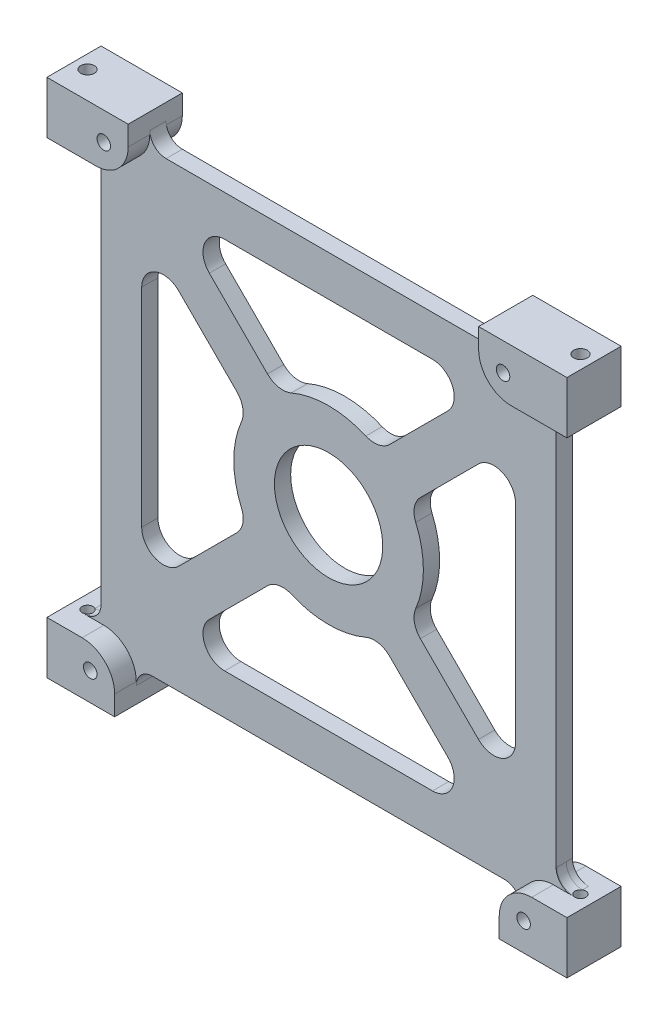
SolidWorks part; units mm, degrees
material "7075-T6 (SN)"
ref_plane "Front Plane" through (0, 0, 0) normal (0, 0, 1) x (1, 0, 0)
ref_plane "Top Plane" through (0, 0, 0) normal (0, 1, 0) x (1, 0, 0)
ref_plane "Right Plane" through (0, 0, 0) normal (1, 0, 0) x (0, 0, -1)
sketch "Sketch1" plane through (0, 0, 0) normal (0, 0, 1) x (1, 0, 0)
  line L0 (-38, 42) -> (-38, 38)
  line L1 (48, -48) -> (-48, -48)
  line L2 (48, -48) -> (48, 48)
  line L3 (48, 48) -> (-48, 48)
  line L4 (-48, -48) -> (-48, 48)
  line L5 (48, -48) -> (-48, 48) construction
  line L6 (48, 48) -> (-48, -48) construction
  line L7 (42, -42) -> (-42, -42)
  line L8 (42, -42) -> (42, 42)
  line L9 (42, 42) -> (-42, 42)
  line L10 (-42, -42) -> (-42, 42)
  line L11 (42, -42) -> (-42, 42) construction
  line L12 (42, 42) -> (-42, -42) construction
  line L13 (-38, 38) -> (-42, 38)
  line L14 (42, 38) -> (38, 38)
  line L15 (38, 38) -> (38, 42)
  line L16 (38, -42) -> (38, -38)
  line L17 (38, -38) -> (42, -38)
  line L18 (-42, -38) -> (-38, -38)
  line L19 (-38, -38) -> (-38, -42)
  point P0 (0, 0)
  point P6 (0, 0)
  point P26 (0, 0)
  dimension "D1" = 96
  dimension "D2" = 96
  dimension "D3" = 6
  dimension "D4" = 84
  dimension "D5" = 10
  dimension "D6" = 4
extrude "Boss-Extrude1" add sketch "Sketch1" along normal blind 10 contours L4 L1 L2 L3 L7 L10 L9 L8 region at (0, -46.6424, 0)
sketch "Sketch4" plane through (0, 0, 10) normal (0, 0, 1) x (1, 0, 0)
  line L0 (36.2, 42.85) -> (-37.5, 42.85) construction
  line L1 (40, -42.85) -> (-40, -42.85) construction
  line L2 (-40, -42.85) -> (-40, 42.85) construction
  line L3 (-40, 42.85) -> (-37.5, 42.85) construction
  line L4 (40, -42.85) -> (40, 42.85) construction
  line L5 (40, 42.85) -> (36.2, 42.85) construction
  line L6 (-40, 42.85) -> (40, -42.85) construction
  point P4 (0, 0)
  dimension "D1" = 73.7
  dimension "D2" = 2.5
  dimension "D3" = 85.7
  dimension "D4" = 3.8
sketch_block_instance "Block1-1"
sketch_block "Block2"
sketch "Sketch5" plane through (0, 0, 10) normal (0, 0, 1) x (1, 0, 0)
  line L0 (40.7, 38.35) -> (42, 38.35)
  line L1 (-42, 47.35) -> (-33, 47.35)
  line L2 (-42, 47.35) -> (-42, 38.35)
  line L3 (-42, 38.35) -> (-33, 38.35)
  line L4 (-33, 47.35) -> (-33, 38.35)
  line L5 (-42, 47.35) -> (-33, 38.35) construction
  line L6 (-42, 38.35) -> (-33, 47.35) construction
  line L7 (-35.5, -47.35) -> (-44.5, -47.35)
  line L8 (-35.5, -47.35) -> (-35.5, -38.35)
  line L9 (-35.5, -38.35) -> (-44.5, -38.35)
  line L10 (-44.5, -47.35) -> (-44.5, -38.35)
  line L11 (-35.5, -47.35) -> (-44.5, -38.35) construction
  line L12 (-35.5, -38.35) -> (-44.5, -47.35) construction
  line L13 (44.5, -47.35) -> (35.5, -47.35)
  line L14 (44.5, -47.35) -> (44.5, -38.35)
  line L15 (44.5, -38.35) -> (35.5, -38.35)
  line L16 (35.5, -47.35) -> (35.5, -38.35)
  line L17 (44.5, -47.35) -> (35.5, -38.35) construction
  line L18 (44.5, -38.35) -> (35.5, -47.35) construction
  line L19 (40.7, 38.35) -> (31.7, 38.35)
  line L20 (40.7, 38.35) -> (40.7, 47.35)
  line L21 (40.7, 47.35) -> (31.7, 47.35)
  line L22 (31.7, 38.35) -> (31.7, 47.35)
  line L23 (40.7, 38.35) -> (31.7, 47.35) construction
  line L24 (40.7, 47.35) -> (31.7, 38.35) construction
  line L25 (42, -42) -> (42, 42) construction
  line L26 (42, 38.35) -> (42, 42)
  line L27 (42, 42) -> (40.7, 42)
  line L28 (42, 42) -> (-42, 42) construction
  point P0 (-37.5, 42.85)
  point P1 (36.2, 42.85)
  point P3 (40, -42.85)
  point P5 (-40, -42.85)
  point P7 (-37.5, 42.85)
  point P13 (-40, -42.85)
  point P18 (40, -42.85)
  point P23 (36.2, 42.85)
  line M13 (42, -42) -> (-42, -42)
  line M14 (-42, -42) -> (-42, 42)
  line M15 (-42, 42) -> (42, 42)
  line M16 (42, 42) -> (42, -42)
  dimension "D1" = 9
  dimension "D2" = 9
  dimension "D3" = 9
  dimension "D4" = 9
  dimension "D5" = 9
  dimension "D6" = 9
  dimension "D7" = 9
  dimension "D8" = 9
extrude "Boss-Extrude2" add sketch "Sketch5" against normal up to surface (10 mm away) contours L22 L19 L20 M15 | L20 L0 M16 M15 | L4 L3 M15 M14 | L8 L9 M14 M13 | L16 L15 M13 M16 region at (41.35, 40.175, 10) region at (36.2, 40.175, 10) region at (38.75, -40.175, 10) region at (-37.5, 40.175, 10) region at (-38.75, -40.175, 10) up to face at (0, 0, 0)
fillet "Fillet1" radius 3 8 edges at (-42, 38.35, 5) (-33, 42, 5) (31.7, 42, 5) (42, 38.35, 5) (35.5, -42, 5) (42, -38.35, 5) (-35.5, -42, 5) (-42, -38.35, 5)
hole_wizard "M3 Tapped Hole1" positions "3DSketch1" profile "Sketch6" tap size "M3" standard "ISO" end condition through all
sketch3d "3DSketch1"
  point P0 (-37.5, 42.85, 10)
  point P3 (36.2, 42.85, 10)
  point P6 (-40, -42.85, 10)
  point P9 (40, -42.85, 10)
  point P12 (0, 0, 0)
  point P13 (0, 0, 0)
cosmetic thread "Hole Thread1" parameters "D2"=3
cosmetic thread "Hole Thread2" parameters "D2"=3
cosmetic thread "Hole Thread3" parameters "D2"=3
cosmetic thread "Hole Thread4" parameters "D2"=3
sketch "Sketch6" plane through (-37.5, 42.85, 10) normal (1, 0, 0) x (0, -1, 0)
  line L0 (0, 0) -> (0, 10)
  line L1 (0, 10) -> (1.25, 10)
  line L2 (1.25, 10) -> (1.25, 0)
  line L5 (1.25, 0) -> (0, 0)
  line L11 (0, -6.35) -> (0, 107.95) construction
  dimension "Thru Tap Drill Dia." = 2.5
  dimension "Thru Tap Drill Depth" = 10
ref_plane "Plane1" through (0, 0, 5) normal (0, 0, -1) x (-1, 0, 0)
sketch "Sketch7" plane through (48, 0, 0) normal (1, 0, 0) x (0, 0, -1)
  line L0 (-5, -48) -> (-5, -32) construction
  line L1 (-10, -48) -> (0, -48) construction
  line L2 (-5, 48) -> (-5, 32) construction
  line L3 (-10, 48) -> (0, 48) construction
  dimension "D1" = 16
  dimension "D2" = 16
ref_plane "Plane2" through (0, 0, 0) normal (0.7071, 0.7071, 0) x (0.7071, -0.7071, 0)
ref_plane "Plane3" through (0, 0, 0) normal (0.7071, -0.7071, 0) x (0, 0, -1)
ref_axis "Axis1" through (0, 0, -0.5) along (0, 0, 1)
sketch "Sketch9" plane through (0, 0, 10) normal (0, 0, 1) x (1, 0, 0)
  line L0 (39, 38.35) -> (43, 38.35)
  line L1 (46, 35.35) -> (46, -35.35)
  line L2 (43, -38.35) -> (39, -38.35)
  line L3 (48, -48) -> (48, 48) construction
  line L24 (39, 38.35) -> (31.7, 38.35)
  line L25 (42, -35.35) -> (42, 35.35)
  line L26 (35.5, -38.35) -> (39, -38.35)
  line L27 (35.5, -42) -> (35.5, -38.35)
  line L28 (-32.5, -45) -> (32.5, -45)
  line L29 (-35.5, -38.35) -> (-35.5, -42)
  line L30 (-42, -38.35) -> (-35.5, -38.35)
  line L31 (-45, 35.35) -> (-45, -35.35)
  line L32 (-33, 38.35) -> (-42, 38.35)
  line L33 (-33, 42) -> (-33, 38.35)
  line L34 (28.7, 45) -> (-30, 45)
  line L35 (31.7, 38.35) -> (31.7, 42)
  line L36 (39, 38.35) -> (31.7, 38.35)
  line L37 (42, -35.35) -> (42, 35.35)
  line L38 (35.5, -38.35) -> (39, -38.35)
  line L39 (35.5, -42) -> (35.5, -38.35)
  line L40 (-32.5, -45) -> (32.5, -45)
  line L41 (-35.5, -38.35) -> (-35.5, -42)
  line L42 (-42, -38.35) -> (-35.5, -38.35)
  line L43 (-45, 35.35) -> (-45, -35.35)
  line L44 (-33, 38.35) -> (-42, 38.35)
  line L45 (-33, 42) -> (-33, 38.35)
  line L46 (28.7, 45) -> (-30, 45)
  line L47 (31.7, 38.35) -> (31.7, 42)
  arc A0 (46, -35.35) -> (43, -38.35) centre (43, -35.35) cw
  arc A1 (43, 38.35) -> (46, 35.35) centre (43, 35.35) cw
  circle A13 centre (40, -42.85) radius 1.7
  circle A14 centre (40, -42.85) radius 1.7
  circle A15 centre (-40, -42.85) radius 1.7
  circle A16 centre (-40, -42.85) radius 1.7
  circle A17 centre (36.2, 42.85) radius 1.7
  circle A18 centre (36.2, 42.85) radius 1.7
  circle A19 centre (-37.5, 42.85) radius 1.7
  circle A20 centre (-37.5, 42.85) radius 1.7
  arc A28 (42, 35.35) -> (39, 38.35) centre (39, 35.35) ccw
  arc A29 (42, 35.35) -> (39, 38.35) centre (39, 35.35) ccw
  arc A30 (32.5, -45) -> (35.5, -42) centre (32.5, -42) ccw
  arc A31 (-35.5, -42) -> (-32.5, -45) centre (-32.5, -42) ccw
  arc A32 (-45, -35.35) -> (-42, -38.35) centre (-42, -35.35) ccw
  arc A33 (-42, 38.35) -> (-45, 35.35) centre (-42, 35.35) ccw
  arc A34 (-30, 45) -> (-33, 42) centre (-30, 42) ccw
  arc A35 (31.7, 42) -> (28.7, 45) centre (28.7, 42) ccw
  arc A36 (39, -38.35) -> (42, -35.35) centre (39, -35.35) ccw
  arc A37 (39, -38.35) -> (42, -35.35) centre (39, -35.35) ccw
  arc A38 (32.5, -45) -> (35.5, -42) centre (32.5, -42) ccw
  arc A39 (-35.5, -42) -> (-32.5, -45) centre (-32.5, -42) ccw
  arc A40 (-45, -35.35) -> (-42, -38.35) centre (-42, -35.35) ccw
  arc A41 (-42, 38.35) -> (-45, 35.35) centre (-42, 35.35) ccw
  arc A42 (-30, 45) -> (-33, 42) centre (-30, 42) ccw
  arc A43 (31.7, 42) -> (28.7, 45) centre (28.7, 42) ccw
  dimension "D7" = 3
  dimension "D6" = 2
  dimension "D1" = 0
  dimension "D2" = 0
  dimension "D3" = 0
  dimension "D4" = 0
  dimension "D5" = 0
extrude "Cut-Extrude1" cut sketch "Sketch9" against normal blind 2.5 contours A1 L0 L2 A0 L1 | L47 A43 L46 A42 L45 | L44 A41 L43 A40 L42 | L41 A39 L40 A38 L39 region at (-1.3591, -0.231, 10) region at (43.9496, 0, 10)
mirror "Mirror1" about plane through (0, 0, 5) normal (0, 0, -1) of "Cut-Extrude1"
sketch "Sketch10" plane through (0, -48, 0) normal (0, -1, 0) x (1, 0, 0)
  line L0 (-48, 5) -> (-45.5, 5) construction
  line L1 (-48, 10) -> (-48, 0) construction
  line L2 (48, 5) -> (45.5, 5) construction
  line L3 (48, 10) -> (48, 0) construction
  dimension "D1" = 2.5
  dimension "D2" = 2.5
hole_wizard "M3 Tapped Hole3" positions "3DSketch3" profile "Sketch11" tap size "M3" standard "ISO"
sketch3d "3DSketch3"
  point P0 (45.5, -48, 5)
  point P3 (-45.5, -48, 5)
sketch "Sketch11" plane through (45.5, -48, 5) normal (1, 0, 0) x (0, 0, -1)
  line L0 (0, 0) -> (0, 10.2511)
  line L1 (0, 10.2511) -> (1.25, 9.5)
  line L2 (1.25, 9.5) -> (1.25, 0)
  line L5 (1.25, 0) -> (0, 0)
  line L10 (0, 10.2511) -> (-1.25, 9.5) construction
  line L11 (0, -6.35) -> (0, 107.95) construction
  dimension "Tap Drill Dia." = 2.5
  dimension "Tap Drill Depth" = 9.5
  dimension "Drill Angle" = 118
cosmetic thread "Hole Thread7" parameters "D1"=8, "D2"=3
cosmetic thread "Hole Thread8" parameters "D1"=8, "D2"=3
mirror "Mirror2" about plane through (0, 0, 0) normal (0, 1, 0) of "M3 Tapped Hole3"
sketch "Sketch12" plane through (48, 0, 0) normal (1, 0, 0) x (0, 0, -1)
  line L0 (-2.8545, 17.3008) -> (-2.8545, 16.9808) construction
  line L1 (-1.8545, 12.4908) -> (-1.8545, 18.0408) construction
  line L2 (-0.6545, 10.1908) -> (1.2455, 10.1908) construction
  line L3 (-0.6545, 20.3408) -> (1.2455, 20.3408) construction
  line L4 (-1.1757, -7.1497) -> (-1.1757, -18.1479) construction
  line L5 (-2.8545, 17.3008) -> (-2.8545, 16.9808)
  line L6 (-1.8545, 12.4908) -> (-1.8545, 18.0408)
  line L7 (-0.6545, 10.1908) -> (1.2455, 10.1908)
  line L8 (-0.6545, 20.3408) -> (1.2455, 20.3408)
  line L9 (-1.1757, -7.1497) -> (-1.1757, -18.1479)
sketch "Sketch13" plane through (0, 0, 10) normal (0, 0, 1) x (1, 0, 0)
  line L0 (-48, -48) -> (-48, 48) construction
  line L1 (-48, 38.35) -> (48, 38.35)
  line L2 (-48, 38.35) -> (-48, -38.35)
  line L3 (-48, -38.35) -> (48, -38.35)
  line L4 (48, 38.35) -> (48, -38.35)
  line L5 (48, -48) -> (48, 48) construction
  line L6 (-42, 38.35) -> (-33, 38.35) construction
  line L7 (-35.5, -38.35) -> (-42, -38.35) construction
  line L8 (48, 48) -> (-48, 48) construction
  line L9 (-33, 38.35) -> (31.7, 38.35)
  line L10 (-33, 38.35) -> (-33, 48)
  line L11 (-33, 48) -> (31.7, 48)
  line L12 (31.7, 38.35) -> (31.7, 48)
  line L13 (31.7, 38.35) -> (31.7, 42) construction
  line L14 (48, -48) -> (-48, -48) construction
  line L15 (-35.5, -38.35) -> (35.5, -38.35)
  line L16 (-35.5, -38.35) -> (-35.5, -48)
  line L17 (-35.5, -48) -> (35.5, -48)
  line L18 (35.5, -38.35) -> (35.5, -48)
  line L19 (35.5, -42) -> (35.5, -38.35) construction
  point P21 (31.7, 40.175)
  arc M13 (28.7, 45) -> (31.7, 42) centre (28.7, 42) cw
  line M14 (31.7, 42) -> (31.7, 38.35)
  line M15 (31.7, 38.35) -> (43, 38.35)
  arc M16 (43, 38.35) -> (46, 35.35) centre (43, 35.35) cw
  line M17 (46, 35.35) -> (46, -35.35)
  arc M18 (46, -35.35) -> (43, -38.35) centre (43, -35.35) cw
  line M19 (43, -38.35) -> (35.5, -38.35)
  line M20 (35.5, -38.35) -> (35.5, -42)
  arc M21 (35.5, -42) -> (32.5, -45) centre (32.5, -42) cw
  line M22 (32.5, -45) -> (-32.5, -45)
  arc M23 (-32.5, -45) -> (-35.5, -42) centre (-32.5, -42) cw
  line M24 (-35.5, -42) -> (-35.5, -38.35)
  line M25 (-35.5, -38.35) -> (-42, -38.35)
  arc M26 (-42, -38.35) -> (-45, -35.35) centre (-42, -35.35) cw
  line M27 (-45, -35.35) -> (-45, 35.35)
  arc M28 (-45, 35.35) -> (-42, 38.35) centre (-42, 35.35) cw
  line M29 (-42, 38.35) -> (-33, 38.35)
  line M30 (-33, 38.35) -> (-33, 42)
  arc M31 (-33, 42) -> (-30, 45) centre (-30, 42) cw
  line M32 (-30, 45) -> (28.7, 45)
  line M37 (-48, 48) -> (-48, -48)
  line M38 (-48, -48) -> (48, -48)
  line M39 (48, -48) -> (48, 48)
  line M40 (48, 48) -> (-48, 48)
extrude "Cut-Extrude3" cut sketch "Sketch13" against normal blind 10 contours L12 L10 M13 M40 M31 M32 | L1 M30 M14 M13 M32 M31 | L3 L1 M37 M26 M27 M28 | L3 L1 M25 M19 M18 M17 M16 M15 M29 M28 M27 M26 | L3 L1 M18 M39 M16 M17 | L18 L16 M21 M22 M23 M38 | L3 M24 M23 M22 M21 M20 region at (-46.4642, 0, 10) region at (0.5, 0, 10) region at (-0.65, 41.6509, 10) region at (-0.65, 46.4577, 10) region at (0, -41.6531, 10) region at (0, -46.4613, 10) region at (46.959, 0, 10)
sketch "Sketch15" plane through (0, 0, 5) normal (0, 0, -1) x (-1, 0, 0)
  line L0 (-34.5, 19.1863) -> (-34.5, -19.1863)
  line L1 (42, 38.35) -> (-42, 38.35)
  line L2 (42, 38.35) -> (42, -38.35)
  line L3 (42, -38.35) -> (-42, -38.35)
  line L4 (-42, 38.35) -> (-42, -38.35)
  line L5 (-48, -38.35) -> (-35.5, -38.35) construction
  line L6 (48, 38.35) -> (48, 48) construction
  line L7 (48, 38.35) -> (33, 38.35) construction
  line L8 (-48, 38.35) -> (-48, 48) construction
  line L9 (33, 48) -> (33, 38.35) construction
  line L10 (33, 38.35) -> (-31.7, 38.35)
  line L11 (33, 38.35) -> (33, 42)
  line L12 (33, 42) -> (-31.7, 42)
  line L13 (-31.7, 38.35) -> (-31.7, 42)
  line L14 (-31.7, 38.35) -> (-31.7, 48) construction
  line L15 (33, 48) -> (48, 48) construction
  line L16 (35.5, -48) -> (35.5, -38.35) construction
  line L17 (35.5, -38.35) -> (-35.5, -38.35)
  line L18 (35.5, -38.35) -> (35.5, -42)
  line L19 (35.5, -42) -> (-35.5, -42)
  line L20 (-35.5, -38.35) -> (-35.5, -42)
  line L21 (-35.5, -48) -> (-35.5, -38.35) construction
  line L22 (-48, -48) -> (-35.5, -48) construction
  line L23 (19.1863, 34.5) -> (-19.1863, 34.5)
  line L24 (0, 0) -> (0, 47.329) construction
  line L25 (0, 0) -> (-34.5, 0) construction
  line L26 (-22.0147, 27.6716) -> (-9.2184, 14.8752)
  line L27 (-14.8752, 9.2184) -> (-27.6716, 22.0147)
  line L28 (-12.3744, 12.3744) -> (-31.9162, 31.9162) construction
  line L29 (-27.6716, -22.0147) -> (-14.8752, -9.2184)
  line L30 (-9.2184, 14.8752) -> (9.2184, 14.8752) construction
  line L31 (-14.8752, 9.2184) -> (-14.8752, -9.2184) construction
  line L32 (9.2184, 14.8752) -> (22.0147, 27.6716)
  line L33 (-19.1863, -34.5) -> (19.1863, -34.5)
  line L34 (-9.2184, -14.8752) -> (-22.0147, -27.6716)
  line L35 (22.0147, -27.6716) -> (9.2184, -14.8752)
  line L36 (14.8752, -9.2184) -> (27.6716, -22.0147)
  line L37 (34.5, -19.1863) -> (34.5, 19.1863)
  line L38 (27.6716, 22.0147) -> (14.8752, 9.2184)
  circle A0 centre (0, 0) radius 17.5
  arc A1 (-34.5, -19.1863) -> (-27.6716, -22.0147) centre (-30.5, -19.1863) ccw
  arc A2 (-27.6716, 22.0147) -> (-34.5, 19.1863) centre (-30.5, 19.1863) ccw
  arc A3 (-19.1863, 34.5) -> (-22.0147, 27.6716) centre (-19.1863, 30.5) ccw
  arc A4 (19.1863, 34.5) -> (22.0147, 27.6716) centre (19.1863, 30.5) cw
  circle A5 centre (0, 0) radius 10
  arc A6 (19.1863, -34.5) -> (22.0147, -27.6716) centre (19.1863, -30.5) ccw
  arc A7 (-19.1863, -34.5) -> (-22.0147, -27.6716) centre (-19.1863, -30.5) cw
  arc A8 (27.6716, -22.0147) -> (34.5, -19.1863) centre (30.5, -19.1863) ccw
  arc A9 (34.5, 19.1863) -> (27.6716, 22.0147) centre (30.5, 19.1863) ccw
  point P38 (0, 34.5)
  point P47 (-34.5, 0)
  point P77 (0, 0)
  dimension "D5" = 35
  dimension "D11" = 4
  dimension "D12" = 20
  dimension "D1" = 6
  dimension "D2" = 6
  dimension "D3" = 6
  dimension "D4" = 6
  dimension "D6" = 7.5
  dimension "D7" = 4
  dimension "D8" = 4
  dimension "D9" = 7.5
  dimension "D10" = 45
  dimension "D13" = 2
extrude "Boss-Extrude3" add sketch "Sketch15" along normal blind 2 and the other way blind 1 contours A0 A5 | L1 L4 L3 L2 L23 A4 L32 A0 L29 A1 L0 A2 L27 L26 A3 | L13 L1 L11 L12 | L3 L20 L19 L18 region at (12.0244, 12.0244, 5) region at (-40.8625, 0, 5) region at (-0.65, 40.175, 5) region at (0, -40.175, 5)
fillet "Fillet2" radius 4 8 edges at (-9.2184, -14.8752, 4.5) (9.2184, -14.8752, 4.5) (14.8752, -9.2184, 4.5) (14.8752, 9.2184, 4.5) (9.2184, 14.8752, 4.5) (-9.2184, 14.8752, 4.5) (-14.8752, -9.2184, 4.5) (-14.8752, 9.2184, 4.5)
fillet "Fillet3" radius 3 8 edges at (-42, 38.35, 4.5) (-42, -38.35, 4.5) (31.7, 42, 4.5) (-33, 42, 4.5) (42, -38.35, 4.5) (-35.5, -42, 4.5) (35.5, -42, 4.5) (42, 38.35, 4.5)
fillet "Fillet4" radius 6 8 edges at (-35.5, -38.35, 1.5) (-33, 38.35, 1.5) (31.7, 38.35, 1.5) (35.5, -38.35, 1.5) (-35.5, -38.35, 8) (35.5, -38.35, 8) (31.7, 38.35, 8) (-33, 38.35, 8)
equation "\"D2@Sketch5\"=\"D1@Sketch5\""
equation "\"D4@Sketch5\"=\"D3@Sketch5\""
equation "\"D5@Sketch5\"=\"D3@Sketch5\""
equation "\"D6@Sketch5\"=\"D3@Sketch5\""
equation "\"D8@Sketch5\"=\"D7@Sketch5\""
equation "\"D2@Sketch7\"=\"D1@Sketch7\""
equation "\"D2@Sketch10\"=\"D1@Sketch10\""
equation "\"D2@Sketch15\"=\"D1@Sketch15\""
equation "\"D3@Sketch15\"=\"D1@Sketch15\""
equation "\"D4@Sketch15\"=\"D1@Sketch15\""
equation "\"D8@Sketch15\"=\"D7@Sketch15\""
equation "\"D9@Sketch15\"=\"D6@Sketch15\""
